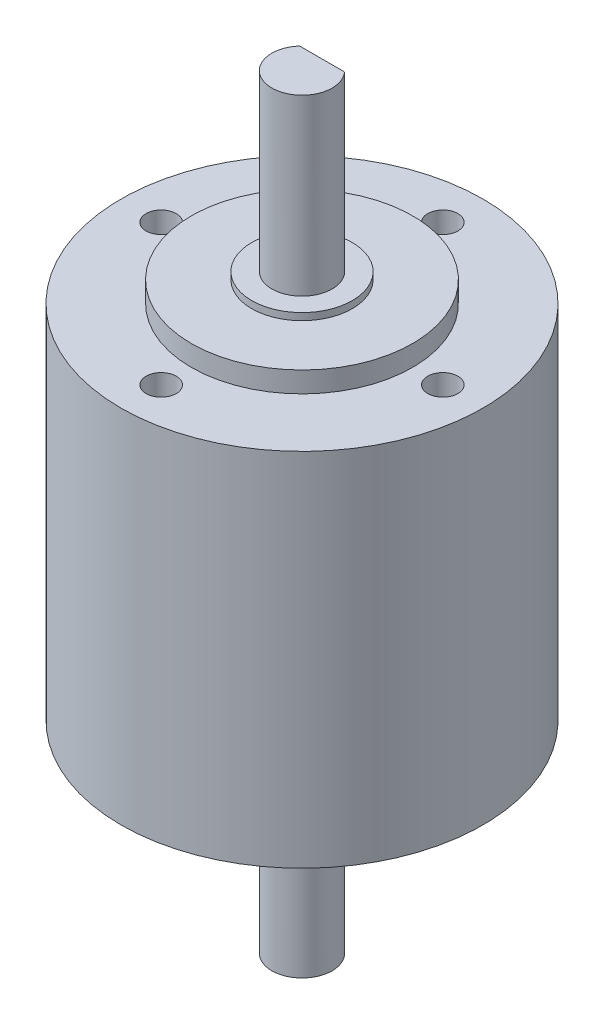
SolidWorks part; units mm, degrees
ref_plane "Front Plane" through (0, 0, 0) normal (0, 0, 1) x (1, 0, 0)
ref_plane "Top Plane" through (0, 0, 0) normal (0, 1, 0) x (1, 0, 0)
ref_plane "Right Plane" through (0, 0, 0) normal (1, 0, 0) x (0, 0, -1)
sketch "Sketch1" plane through (0, 0, 0) normal (0, 1, 0) x (1, 0, 0)
  circle A0 centre (0, 0) radius 18
  dimension "D1" = 36
extrude "Boss-Extrude1" add sketch "Sketch1" along normal mid plane 35.8902
sketch "Sketch2" plane through (0, 17.9451, 0) normal (0, 1, 0) x (1, 0, 0)
  circle A0 centre (0, 0) radius 11
  dimension "D1" = 22
extrude "Boss-Extrude2" add sketch "Sketch2" along normal mid plane 40.005 from surface starting at plane "Top Plane"
sketch "Sketch3" plane through (0, 20.0025, 0) normal (0, 1, 0) x (1, 0, 0)
  circle A0 centre (0, 0) radius 3
  dimension "D1" = 6
extrude "Boss-Extrude4" add sketch "Sketch3" along normal blind 18
sketch "Sketch4" plane through (0, 38.0025, 0) normal (0, 1, 0) x (1, 0, 0)
  line L0 (-2.2361, 2) -> (2.2361, 2)
  line L1 (0, -3) -> (0, 2) construction
  arc A0 (0, -3) -> (2.2361, 2) centre (0, 0) ccw construction
  circle A1 centre (0, 0) radius 3
  arc A2 (2.2361, 2) -> (-2.2361, 2) centre (0, 0) ccw
  arc A3 (-2.2361, 2) -> (0, -3) centre (0, 0) ccw construction
  dimension "D2" = 5
  dimension "D1" = 0
extrude "Cut-Extrude1" cut sketch "Sketch4" against normal blind 15
sketch "Sketch5" plane through (0, 17.9451, 0) normal (0, 1, 0) x (1, 0, 0)
  circle A0 centre (0, 0) radius 14 construction
  circle A1 centre (0, 14) radius 1.5
  circle A2 centre (-14, 0) radius 1.5
  circle A3 centre (0, -14) radius 1.5
  circle A4 centre (14, 0) radius 1.5
  dimension "D1" = 28
  dimension "D2" = 3
extrude "Cut-Extrude2" cut sketch "Sketch5" against normal blind 4
mirror "Mirror1" about plane through (0, 0, 0) normal (0, 1, 0) of "Cut-Extrude2", "Cut-Extrude1"
sketch "Sketch6" plane through (0, -20.0025, 0) normal (0, -1, 0) x (1, 0, 0)
  circle A0 centre (0, 0) radius 3
  dimension "D1" = 6
extrude "Boss-Extrude5" add sketch "Sketch6" along normal blind 18
sketch "Sketch7" plane through (0, -38.0025, 0) normal (0, -1, 0) x (1, 0, 0)
  line L0 (-2.2361, -2) -> (2.2361, -2)
  line L1 (0, -2) -> (0, -3) construction
  arc A0 (2.2361, -2) -> (-2.2361, -2) centre (0, 0) cw
  circle A2 centre (0, 0) radius 3 construction
  dimension "D1" = 1
extrude "Cut-Extrude3" cut sketch "Sketch7" against normal offset from surface (15 mm away) 3 up to face at (0, -20.0025, -3)
sketch "Sketch9" plane through (0, 0, 0) normal (0, 1, 0) x (1, 0, 0)
  circle A0 centre (0, 0) radius 5
  dimension "D1" = 10
extrude "Boss-Extrude6" add sketch "Sketch9" along normal mid plane 41.402
